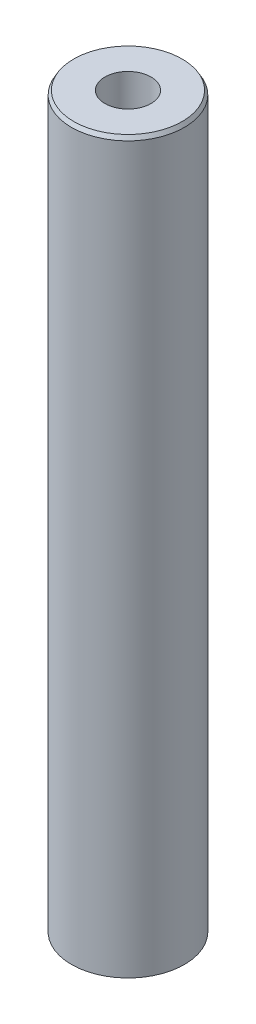
SolidWorks part; units mm, degrees
ref_plane "Front Plane" through (0, 0, 0) normal (0, 0, 1) x (1, 0, 0)
ref_plane "Top Plane" through (0, 0, 0) normal (0, 1, 0) x (1, 0, 0)
ref_plane "Right Plane" through (0, 0, 0) normal (1, 0, 0) x (0, 0, -1)
sketch "Sketch1" plane through (0, 0, 0) normal (0, 1, 0) x (1, 0, 0)
  circle A0 centre (0, 0) radius 10
  dimension "SHAFT_OD" = 20
extrude "Boss-Extrude1" add sketch "Sketch1" along normal blind 129.465
sketch "Sketch2" plane through (0, 0, 0) normal (0, 1, 0) x (1, 0, 0)
  circle A0 centre (0, 0) radius 4.0822
  dimension "BORE_D" = 8.1643
extrude "Cut-Extrude1" cut sketch "Sketch2" along normal through all
chamfer "Chamfer1" distance 0.6973 angle 30 2 edges at (0, 129.465, 10) (0, 0, 10) first distance on face at (0, 129.465, 10) first distance on face at (0, 0, 4.0822)
